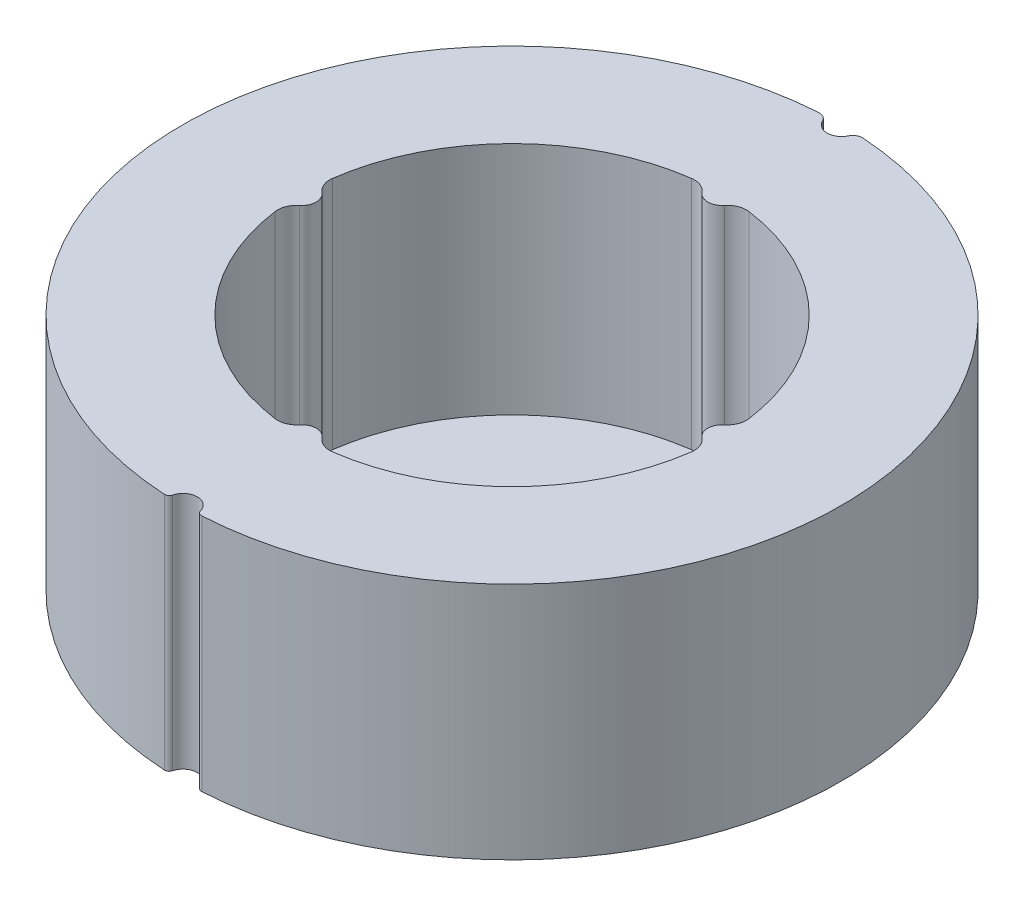
SolidWorks part; units mm, degrees
ref_plane "Front Plane" through (0, 0, 0) normal (0, 0, 1) x (1, 0, 0)
ref_plane "Top Plane" through (0, 0, 0) normal (0, 1, 0) x (1, 0, 0)
ref_plane "Right Plane" through (0, 0, 0) normal (1, 0, 0) x (0, 0, -1)
sketch "Sketch1" plane through (0, 0, 0) normal (0, 1, 0) x (1, 0, 0)
  line L3 (0, 0.002) -> (0, 3.7877) construction
  line L4 (0, 3.7877) -> (2.417, 3.7877)
  line L5 (0, 3.7877) -> (-2.417, 3.7877)
  arc A0 (1.9642, -34.442) -> (34.1982, 4.5552) centre (0, 0.002) ccw
  arc A2 (-2.417, 3.7877) -> (2.417, 3.7877) centre (0, 0.002) ccw
  circle A3 centre (0, 0.002) radius 34.5 construction
  arc A7 (-1.3541, 33.8562) -> (1.3541, 33.8562) centre (0, 34.5015) ccw
  arc A8 (34.1982, 4.5552) -> (2.3241, 34.4236) centre (0, 0.002) ccw
  arc A9 (-2.3241, 34.4236) -> (-34.1982, 4.5552) centre (0, 0.002) ccw
  arc A10 (-34.1982, 4.5552) -> (-1.9642, -34.442) centre (0, 0.002) ccw
  arc A11 (1.3541, 33.8562) -> (2.3241, 34.4236) centre (2.2568, 33.4259) cw
  arc A12 (-1.3541, 33.8562) -> (-2.3241, 34.4236) centre (-2.2568, 33.4259) ccw
  arc A13 (1.4518, -34.0686) -> (-1.4518, -34.0686) centre (0, -34.4457) ccw
  arc A14 (1.4518, -34.0686) -> (1.9642, -34.442) centre (1.9358, -33.9428) ccw
  arc A15 (-1.4518, -34.0686) -> (-1.9642, -34.442) centre (-1.9358, -33.9428) cw
  point P15 (1.4997, 34.4694)
  dimension "D2" = 4.834
  dimension "D3" = 4.4915
  dimension "D4" = 34.5
  dimension "D5" = 1
  dimension "D6" = 1.5
  dimension "D7" = 0.5
  dimension "D11" = 1.4997
sketch "Sketch2" plane through (0, 0, 0) normal (0, 1, 0) x (1, 0, 0)
  arc A0 (-21.7937, -3.0054) -> (-3.0054, -21.7937) centre (0, 0) ccw
  arc A1 (-1.1709, 21.0625) -> (1.1709, 21.0625) centre (0, 22) ccw
  arc A2 (21.0625, 1.1709) -> (21.0625, -1.1709) centre (22, 0) ccw
  arc A3 (1.1709, -21.0625) -> (-1.1709, -21.0625) centre (0, -22) ccw
  arc A4 (-21.0625, -1.1709) -> (-21.0625, 1.1709) centre (-22, 0) ccw
  arc A5 (-3.0054, 21.7937) -> (-21.7937, 3.0054) centre (0, 0) ccw
  arc A6 (21.7937, 3.0054) -> (3.0054, 21.7937) centre (0, 0) ccw
  arc A7 (3.0054, -21.7937) -> (21.7937, -3.0054) centre (0, 0) ccw
  arc A8 (-21.0625, -1.1709) -> (-21.7937, -3.0054) centre (-19.8125, -2.7322) ccw
  arc A9 (-21.0625, 1.1709) -> (-21.7937, 3.0054) centre (-19.8125, 2.7322) cw
  arc A10 (1.1709, -21.0625) -> (3.0054, -21.7937) centre (2.7322, -19.8125) ccw
  arc A11 (-1.1709, -21.0625) -> (-3.0054, -21.7937) centre (-2.7322, -19.8125) cw
  arc A12 (21.0625, 1.1709) -> (21.7937, 3.0054) centre (19.8125, 2.7322) ccw
  arc A13 (21.0625, -1.1709) -> (21.7937, -3.0054) centre (19.8125, -2.7322) cw
  arc A14 (1.1709, 21.0625) -> (3.0054, 21.7937) centre (2.7322, 19.8125) cw
  arc A15 (-1.1709, 21.0625) -> (-3.0054, 21.7937) centre (-2.7322, 19.8125) ccw
  point P21 (1.4991, -21.9489)
  point P26 (21.9489, 1.4991)
  point P33 (-1.4991, 21.9489)
  dimension "D1" = 22
  dimension "D2" = 1.5
  dimension "D3" = 1.5
  dimension "D4" = 1.5
  dimension "D5" = 1.5
  dimension "D6" = 2
extrude "Boss-Extrude1" add sketch "Sketch1" along normal blind 25 contours A10 A0 A8 A7 A9 A2 L5 L4 region at (2.2155, 0, 33.5591)
extrude "Cut-Extrude2" cut sketch "Sketch2" along normal through all
extrude "Boss-Extrude2" add sketch "Sketch2<2>" along normal blind 0.4
sketch "Sketch2<2>" plane through (0, 0, 0) normal (0, 1, 0) x (1, 0, 0) same geometry as "Sketch2"
